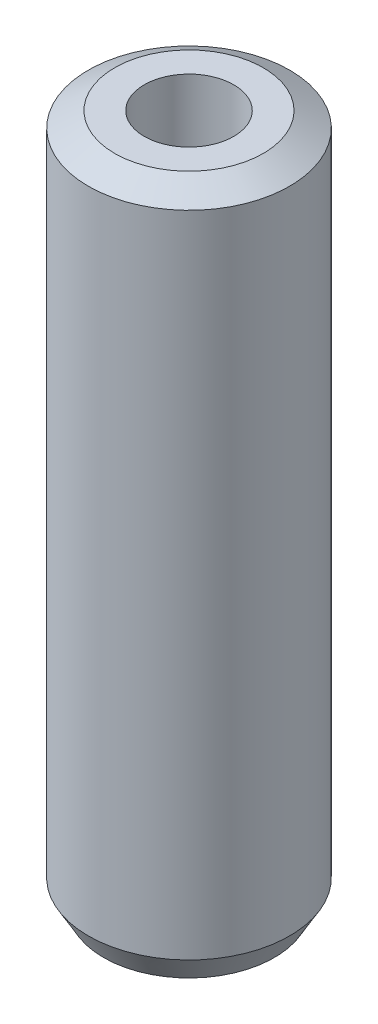
SolidWorks part; units mm, degrees
ref_plane "Front Plane" through (0, 0, 0) normal (0, 0, 1) x (1, 0, 0)
ref_plane "Top Plane" through (0, 0, 0) normal (0, 1, 0) x (1, 0, 0)
ref_plane "Right Plane" through (0, 0, 0) normal (1, 0, 0) x (0, 0, -1)
sketch "Sketch1" plane through (0, 0, 0) normal (0, 1, 0) x (1, 0, 0)
  circle A0 centre (0, 0) radius 10
  dimension "SHAFT_OD" = 20
extrude "Boss-Extrude1" add sketch "Sketch1" along normal blind 68.6373
sketch "Sketch2" plane through (0, 0, 0) normal (0, 1, 0) x (1, 0, 0)
  circle A0 centre (0, 0) radius 4.447
  dimension "BORE_D" = 8.8941
extrude "Cut-Extrude1" cut sketch "Sketch2" along normal through all
chamfer "Chamfer1" distance 1.5115 angle 60 2 edges at (0, 68.6373, 10) (0, 0, 10) first distance on face at (0, 68.6373, 10) first distance on face at (0, 0, 4.447)
